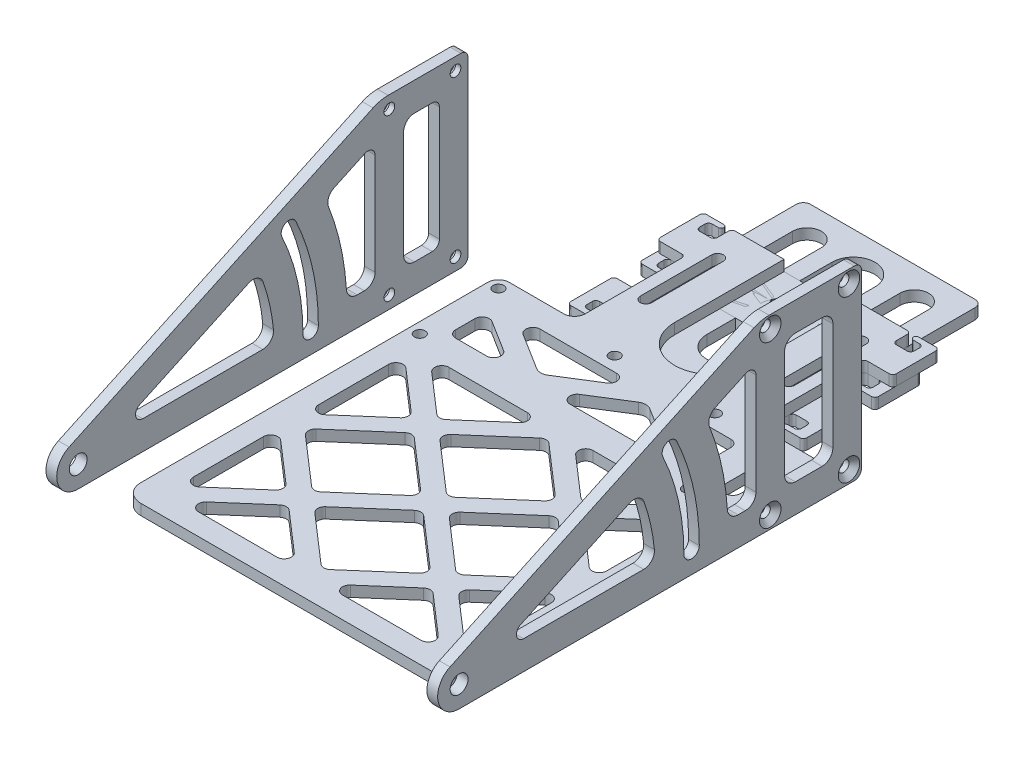
SolidWorks part; units mm, degrees
material "Thornel Mat VMA"
ref_plane "前视基准面" through (0, 0, 0) normal (0, 0, 1) x (1, 0, 0)
ref_plane "上视基准面" through (0, 0, 0) normal (0, 1, 0) x (1, 0, 0)
ref_plane "右视基准面" through (0, 0, 0) normal (1, 0, 0) x (0, 0, -1)
sketch "草图1" plane through (0, 0, 0) normal (1, 0, 0) x (0, 0, -1)
  line L0 (-53.59, 7.4702) -> (-112.5, -20) construction
  line L3 (0, 24) -> (0, -24)
  line L5 (-3.5, 22.5) -> (-3.5, -22.5) construction
  line L6 (-3.5, 22.5) -> (-25.5, 22.5) construction
  line L7 (-25.5, 22.5) -> (-25.5, -22.5) construction
  line L8 (-3.5, -22.5) -> (-25.5, -22.5) construction
  line L25 (-112.5, -26) -> (-2, -26)
  line L27 (-30.0591, 25.0631) -> (-115.0357, -14.5622)
  line L28 (-25.8329, 26) -> (-2, 26)
  line L29 (-112.5, -20) -> (-47.5, -20) construction
  circle A0 centre (-3.5, 22.5) radius 1.5
  circle A1 centre (-25.5, 22.5) radius 1.5
  circle A2 centre (-25.5, -22.5) radius 1.5
  circle A3 centre (-3.5, -22.5) radius 1.5
  arc A6 (-115.0357, -14.5622) -> (-112.5, -26) centre (-112.5, -20) ccw
  circle A7 centre (-112.5, -20) radius 2.5
  arc A8 (0, -24) -> (-2, -26) centre (-2, -24) cw
  arc A9 (-2, 26) -> (0, 24) centre (-2, 24) cw
  arc A11 (-47.5, -20) -> (-53.59, 7.4702) centre (-112.5, -20) ccw construction
  arc A12 (-45.35, -20) -> (-51.6414, 8.3788) centre (-112.5, -20) ccw
  arc A13 (-49.65, -20) -> (-55.5386, 6.5616) centre (-112.5, -20) ccw
  arc A14 (-49.65, -20) -> (-45.35, -20) centre (-47.5, -20) ccw
  arc A15 (-51.6414, 8.3788) -> (-55.5386, 6.5616) centre (-53.59, 7.4702) ccw
  arc A16 (-30.0591, 25.0631) -> (-25.8329, 26) centre (-25.8329, 16) cw
  point P20 (-49.0408, -5.9314)
  dimension "D5" = 3
  dimension "D6" = 3.5
  dimension "D10" = 4.3
  dimension "D11" = 3.5
  dimension "D12" = 65
  dimension "D3" = 6
  dimension "D4" = 5
  dimension "D8" = 2
  dimension "D9" = 112.5
  dimension "D14" = 10
  dimension "D1" = 22
  dimension "D2" = 45
  dimension "D7" = 3.5
  dimension "D13" = 25
extrude "凸台-拉伸1" add sketch "草图1" along normal blind 3 from offset 51.75
hole_wizard "孔1" positions "草图7" profile "草图8" legacy end condition through all
sketch "草图7" plane through (54.75, 0, 0) normal (1, 0, 0) x (0, 0, -1)
  point P0 (-25.5, 22.5)
  point P3 (-3.5, 22.5)
  point P6 (-3.5, -22.5)
  point P9 (-25.5, -22.5)
sketch "草图8" plane through (54.75, 22.5, 25.5) normal (0, 1, 0) x (0, 0, -1)
  line L0 (0, 0) -> (0, 3)
  line L1 (0, 3) -> (1.5, 3)
  line L2 (1.5, 3) -> (1.5, 1.5)
  line L3 (1.5, 1.5) -> (3, 0)
  line L4 (3, 0) -> (0, 0)
  line L5 (0, -6.4453) -> (0, 115.525) construction
  line L6 (-1.5, 1.5) -> (-3, 0) construction
  dimension "直径" = 3
  dimension "深度" = 3
  dimension "锥坑角度" = 90
  dimension "锥坑直径" = 6
sketch "草图11" plane through (54.75, 0, 0) normal (1, 0, 0) x (0, 0, -1)
  line L0 (-34.5101, -18) -> (-32.5, -18)
  line L1 (-25.5, 22.5) -> (-25.5, -22.5) construction
  line L2 (-29.5, 13.3574) -> (-29.5, -15)
  line L3 (-21.5, 15) -> (-21.5, -15)
  line L4 (-64.8817, -0.002) -> (-95.3024, -14.1874)
  line L5 (-29.5, 22.5) -> (-29.5, -22.5) construction
  line L6 (-21.5, 22.5) -> (-21.5, -22.5) construction
  line L7 (-18.5, -18) -> (-11, -18)
  line L8 (-103.4786, -18) -> (-8, -18)
  line L9 (-8, -18) -> (-8, 18)
  line L10 (-8, 18) -> (-25.8329, 18)
  line L11 (-26.6782, 17.8126) -> (-103.4786, -18)
  line L12 (-94.4572, -18) -> (-60.8916, -18)
  line L13 (-8, -15) -> (-8, 15)
  line L14 (-11, 18) -> (-18.5, 18)
  line L15 (-32.3452, 15.17) -> (-40.9719, 11.1473)
  arc A0 (-29.5, 13.3574) -> (-32.3452, 15.17) centre (-31.5, 13.3574) ccw
  arc A1 (-94.4572, -18) -> (-95.3024, -14.1874) centre (-94.4572, -16) cw
  arc A2 (-21.5, 15) -> (-18.5, 18) centre (-18.5, 15) cw
  arc A3 (-11, 18) -> (-8, 15) centre (-11, 15) cw
  arc A4 (-8, -15) -> (-11, -18) centre (-11, -15) cw
  arc A5 (-18.5, -18) -> (-21.5, -15) centre (-18.5, -15) cw
  arc A6 (-57.65, -20) -> (-62.789, 3.1806) centre (-112.5, -20) ccw
  arc A7 (-57.9056, -14.7107) -> (-60.7853, -1.7212) centre (-112.5, -20) ccw
  arc A8 (-25.8329, 18) -> (-26.6782, 17.8126) centre (-25.8329, 16) ccw
  arc A10 (-40.9719, 11.1473) -> (-42.4985, 7.3371) centre (-39.7041, 8.4284) ccw
  arc A11 (-37.35, -20) -> (-44.391, 11.7598) centre (-112.5, -20) ccw
  arc A12 (-37.504, -15.1919) -> (-42.4985, 7.3371) centre (-112.5, -20) ccw
  arc A13 (-29.5, -15) -> (-32.5, -18) centre (-32.5, -15) cw
  arc A14 (-34.5101, -18) -> (-37.504, -15.1919) centre (-34.5101, -15) cw
  arc A15 (-60.8916, -18) -> (-57.9056, -14.7107) centre (-60.8916, -15) ccw
  arc A16 (-64.8817, -0.002) -> (-60.7853, -1.7212) centre (-63.6139, -2.7209) cw
  dimension "D6" = 2
  dimension "D7" = 3
  dimension "D4" = 4
  dimension "D1" = 8
  dimension "D2" = 8
  dimension "D3" = 8
  dimension "D5" = 4
extrude "切除-拉伸2" cut sketch "草图11" against normal through all
mirror "镜向1" about plane through (0, 0, 0) normal (1, 0, 0) of bodies 121 106
sketch "草图2" plane through (-54.75, 0, 0) normal (-1, 0, 0) x (0, 0, 1)
  circle A0 centre (3.5, -22.5) radius 3 construction
  circle A3 centre (3.5, 22.5) radius 3 construction
  circle A4 centre (3.5, -22.5) radius 3
  circle A5 centre (3.5, 22.5) radius 3
extrude "凸台-拉伸2" add sketch "草图2" against normal up to surface (3 mm away) up to face at (-51.75, 0, 14.75)
sketch "草图4" plane through (-54.75, 0, 0) normal (-1, 0, 0) x (0, 0, 1)
  line L1 (25.5, 22.5) -> (7, 22.5) construction
  line L2 (25.5, 22.5) -> (25.5, -22.5) construction
  line L3 (25.5, -22.5) -> (7, -22.5) construction
  line L4 (7, 22.5) -> (7, -22.5) construction
  line L5 (0, 26) -> (3.5, 26)
  line L6 (0, 26) -> (0, -26)
  line L7 (0, -26) -> (3.5, -26)
  line L12 (3.5, 26) -> (3.5, -26)
  line L13 (2, 26) -> (25.8329, 26) construction
  line L14 (112.5, -26) -> (2, -26) construction
  line L15 (0, -24) -> (0, 24) construction
  circle A1 centre (25.5, 22.5) radius 1.5 construction
  circle A8 centre (7, -22.5) radius 1.5
  circle A9 centre (7, 22.5) radius 1.5
  dimension "D1" = 18.5
  dimension "D2" = 3.5
extrude "切除-拉伸1" cut sketch "草图4" against normal through all
other "移动面1" face at (-53.25, -16.8107, 9.1893) face at (-53.25, 16.8107, 9.1893) face at (-53.25, 0, 8) offset 3.5 parameters "D1"=3.5
fillet "圆角3" radius 2 4 edges at (-53.25, -26, 3.5) (-53.25, 26, 3.5) (-53.25, -18, 11.5) (-53.25, 18, 11.5)
hole_wizard "孔2" positions "草图9" profile "草图10" legacy end condition through all
sketch "草图9" plane through (-54.75, 0, 0) normal (-1, 0, 0) x (0, 0, 1)
  point P0 (7, 22.5)
  point P3 (7, -22.5)
sketch "草图10" plane through (-54.75, 22.5, 7) normal (0, 1, 0) x (0, 0, 1)
  line L0 (0, 0) -> (0, 109.5)
  line L1 (0, 109.5) -> (1.5, 109.5)
  line L2 (1.5, 109.5) -> (1.5, 1.5)
  line L3 (1.5, 1.5) -> (3, 0)
  line L4 (3, 0) -> (0, 0)
  line L5 (0, -6.4453) -> (0, 115.525) construction
  line L6 (-1.5, 1.5) -> (-3, 0) construction
  dimension "直径" = 3
  dimension "深度" = 109.5
  dimension "锥坑角度" = 90
  dimension "锥坑直径" = 6
ref_plane "基准面1" through (0, -27.7, 0) normal (0, -1, 0) x (-1, 0, 0)
sketch "草图5" plane through (0, -27.7, 0) normal (0, -1, 0) x (-1, 0, 0)
  line L0 (0, 0) -> (0, 43.5) construction
  line L3 (-33, 43.5) -> (-27.25, 43.5)
  line L4 (46.25, -100.5) -> (46.25, -3.5)
  line L5 (-20, 34.5) -> (-20, 14.5) construction
  line L6 (-31.75, -3.5) -> (43.25, -3.5) construction
  line L7 (-31.75, -3.5) -> (-31.75, -25.5) construction
  line L8 (-31.75, -25.5) -> (43.25, -25.5) construction
  line L9 (43.25, -3.5) -> (43.25, -25.5) construction
  line L11 (28, -0.5) -> (43.25, -0.5)
  line L12 (-18.4, 34.5) -> (-18.4, 14.5)
  line L13 (-21.6, 34.5) -> (-21.6, 14.5)
  line L14 (-25, 43.5) -> (25, 43.5)
  line L16 (-30, 42) -> (-30, 38.5)
  line L17 (-30, 38.5) -> (-25, 38.5)
  line L18 (-25, 43.5) -> (-25, 38.5)
  line L19 (-33, 30.5) -> (-33, 43.5)
  line L20 (-33, 30.5) -> (-25, 30.5)
  line L22 (-43.25, -0.5) -> (-28, -0.5)
  line L23 (-25, 30.5) -> (-25, 2.5)
  line L24 (-20, 34.5) -> (-25, 34.5) construction
  line L25 (-25, 30.5) -> (-25, 38.5) construction
  line L26 (0, 28.6) -> (0, -28.6) construction
  line L27 (25, 30.5) -> (25, 38.5) construction
  line L28 (20, 34.5) -> (25, 34.5) construction
  line L29 (25, 30.5) -> (25, 2.5)
  line L30 (33, 30.5) -> (25, 30.5)
  line L31 (33, 30.5) -> (33, 43.5)
  line L32 (25, 43.5) -> (25, 38.5)
  line L33 (30, 38.5) -> (25, 38.5)
  line L34 (30, 42) -> (30, 38.5)
  line L35 (33, 43.5) -> (27.25, 43.5)
  line L36 (20, 34.5) -> (20, 14.5) construction
  line L37 (18.4, 34.5) -> (18.4, 14.5)
  line L38 (21.6, 34.5) -> (21.6, 14.5)
  line L43 (41.25, -105.5) -> (-41.25, -105.5)
  line L44 (-46.25, -100.5) -> (-46.25, -3.5)
  line L45 (-30, 42) -> (-27.25, 42)
  line L46 (30, 42) -> (27.25, 42)
  arc A0 (-18.4, 34.5) -> (-21.6, 34.5) centre (-20, 34.5) ccw
  circle A1 centre (-31.75, -25.5) radius 1.5
  arc A2 (-21.6, 14.5) -> (-18.4, 14.5) centre (-20, 14.5) ccw
  arc A4 (-28, -0.5) -> (-25, 2.5) centre (-28, 2.5) ccw
  arc A5 (28, -0.5) -> (25, 2.5) centre (28, 2.5) cw
  arc A6 (18.4, 34.5) -> (21.6, 34.5) centre (20, 34.5) cw
  circle A7 centre (10.75, -3.5) radius 1.5
  circle A8 centre (-17.25, -3.5) radius 1.5
  circle A9 centre (-31.75, -3.5) radius 1.5
  circle A10 centre (43.25, -3.5) radius 1.5
  circle A11 centre (43.25, -25.5) radius 1.5
  arc A12 (43.25, -0.5) -> (46.25, -3.5) centre (43.25, -3.5) cw
  arc A16 (21.6, 14.5) -> (18.4, 14.5) centre (20, 14.5) cw
  arc A21 (46.25, -100.5) -> (41.25, -105.5) centre (41.25, -100.5) cw
  arc A22 (-43.25, -0.5) -> (-46.25, -3.5) centre (-43.25, -3.5) ccw
  arc A23 (-46.25, -100.5) -> (-41.25, -105.5) centre (-41.25, -100.5) ccw
  arc A24 (-27.25, 43.5) -> (-27.25, 42) centre (-27.25, 42.75) cw
  arc A25 (27.25, 43.5) -> (27.25, 42) centre (27.25, 42.75) ccw
  point P3 (-20, 24.5)
  point P62 (20, 24.5)
  point P70 (-26.5, 42.75)
  dimension "D5" = 3
  dimension "D8" = 28
  dimension "D9" = 14.5
  dimension "D12" = 3
  dimension "D13" = 8
  dimension "D17" = 50
  dimension "D18" = 5
  dimension "D6" = 3
  dimension "D20" = 1.5
  dimension "D1" = 3.5
  dimension "D2" = 22
  dimension "D3" = 75
  dimension "D4" = 31.75
  dimension "D7" = 43.5
  dimension "D10" = 20
  dimension "D11" = 3.2
  dimension "D14" = 5
  dimension "D15" = 5
  dimension "D16" = 5
  dimension "D19" = 80
  dimension "D21" = 1.5
extrude "凸台-拉伸3" add sketch "草图5" along normal blind 3 separate body
sketch "草图6" plane through (0, -30.7, 0) normal (0, -1, 0) x (1, 0, 0)
  line L0 (33, -30.5) -> (25, -30.5) construction
  line L1 (33, -43.5) -> (33, -30.5) construction
  line L2 (30, -38.5) -> (30, -42) construction
  line L3 (25, -38.5) -> (30, -38.5) construction
  line L4 (30, -30.5) -> (25, -30.5)
  line L5 (33, -38.5) -> (33, -25.5)
  line L6 (30, -27) -> (30, -30.5)
  line L7 (25, -38.5) -> (33, -38.5)
  line L9 (25, -30.5) -> (25, -2.5) construction
  line L10 (25, -30.5) -> (25, -25.5)
  line L11 (25, -43.5) -> (25, -38.5) construction
  line L12 (25, -61.5) -> (25, -38.5)
  line L13 (25, -25.5) -> (-25, -25.5)
  line L14 (23, -63.5) -> (-23, -63.5)
  line L15 (-25, -43.5) -> (25, -43.5) construction
  line L16 (0, -28.6) -> (0, 28.6) construction
  line L17 (-25, -61.5) -> (-25, -38.5)
  line L18 (-25, -30.5) -> (-25, -25.5)
  line L20 (-25, -38.5) -> (-33, -38.5)
  line L21 (-30, -27) -> (-30, -30.5)
  line L22 (-33, -38.5) -> (-33, -25.5)
  line L23 (-30, -30.5) -> (-25, -30.5)
  line L24 (33, -25.5) -> (27.25, -25.5)
  line L25 (27.25, -27) -> (30, -27)
  line L26 (27.25, -42.75) -> (27.25, -26.25) construction
  line L27 (-27.25, -27) -> (-30, -27)
  line L28 (-33, -25.5) -> (-27.25, -25.5)
  circle A0 centre (20, -34.5) radius 1.5
  circle A1 centre (-20, -34.5) radius 1.5
  arc A2 (25, -61.5) -> (23, -63.5) centre (23, -61.5) cw
  arc A3 (-25, -61.5) -> (-23, -63.5) centre (-23, -61.5) ccw
  arc A4 (27.25, -27) -> (27.25, -25.5) centre (27.25, -26.25) cw
  arc A5 (-27.25, -27) -> (-27.25, -25.5) centre (-27.25, -26.25) ccw
  dimension "D1" = 3
  dimension "D3" = 2
  dimension "D2" = 20
extrude "凸台-拉伸4" add sketch "草图6" along normal blind 3 separate body
fillet "圆角1" radius 1 14 edges at (25, -29.2, -30.5) (33, -29.2, -30.5) (33, -29.2, -43.5) (30, -29.2, -38.5) (25, -29.2, -38.5) (25, -29.2, -43.5) (-25, -29.2, -43.5) (-25, -29.2, -38.5) (-25, -29.2, -30.5) (-33, -29.2, -30.5) (-33, -29.2, -43.5) (-30, -29.2, -38.5) (30, -29.2, -42) (-30, -29.2, -42)
fillet "圆角2" radius 1 14 edges at (25, -32.2, -30.5) (30, -32.2, -30.5) (33, -32.2, -38.5) (25, -32.2, -38.5) (-25, -32.2, -38.5) (-33, -32.2, -38.5) (-30, -32.2, -30.5) (-25, -32.2, -30.5) (-25, -32.2, -25.5) (25, -32.2, -25.5) (33, -32.2, -25.5) (30, -32.2, -27) (-33, -32.2, -25.5) (-30, -32.2, -27)
sketch "草图12" plane through (0, -33.7, 0) normal (0, -1, 0) x (1, 0, 0)
  line L0 (-15, -42.5) -> (-15, -54.5) construction
  line L1 (-11, -42.5) -> (-11, -54.5)
  line L2 (-19, -42.5) -> (-19, -54.5)
  line L3 (0, -37.5) -> (0, -52.5) construction
  line L4 (6, -37.5) -> (6, -52.5)
  line L5 (-6, -37.5) -> (-6, -52.5)
  line L8 (-23, -58.5) -> (23, -58.5)
  line L9 (-23, -58.5) -> (23, -58.5) construction
  line L10 (-25, -39.5) -> (-25, -61.5) construction
  line L11 (24, -25.5) -> (-24, -25.5) construction
  line L12 (0, -32.835) -> (0, 32.835) construction
  line L16 (15, -42.5) -> (15, -54.5) construction
  line L17 (11, -42.5) -> (11, -54.5)
  line L18 (19, -42.5) -> (19, -54.5)
  arc A0 (-11, -42.5) -> (-19, -42.5) centre (-15, -42.5) ccw
  arc A1 (-19, -54.5) -> (-11, -54.5) centre (-15, -54.5) ccw
  arc A2 (6, -37.5) -> (-6, -37.5) centre (0, -37.5) ccw
  arc A3 (-6, -52.5) -> (6, -52.5) centre (0, -52.5) ccw
  arc A6 (11, -42.5) -> (19, -42.5) centre (15, -42.5) cw
  arc A7 (19, -54.5) -> (11, -54.5) centre (15, -54.5) cw
  point P2 (-15, -48.5)
  point P7 (0, -45)
  point P24 (0, -31.5)
  point P38 (15, -48.5)
  dimension "D1" = 5
  dimension "D2" = 6
  dimension "D3" = 12
  dimension "D4" = 5
  dimension "D5" = 12
  dimension "D6" = 6
extrude "切除-拉伸3" cut sketch "草图12" against normal through all
sketch "草图13" plane through (0, -30.7, 0) normal (0, -1, 0) x (1, 0, 0)
  line L0 (38, 19.25) -> (38, 9.75) construction
  line L1 (-40.25, 99.5) -> (40.25, 99.5)
  line L2 (-40.25, 99.5) -> (-40.25, 29.5)
  line L3 (-40.25, 29.5) -> (40.25, 29.5)
  line L4 (40.25, 99.5) -> (40.25, 29.5)
  line L5 (-39.25, 21.5) -> (27.75, 21.5)
  line L6 (-39.25, 21.5) -> (-39.25, 7.5)
  line L7 (-39.25, 7.5) -> (27.75, 7.5)
  line L8 (27.75, 21.5) -> (27.75, 7.5)
  line L13 (40.25, 19.25) -> (40.25, 9.75)
  line L14 (35.75, 19.25) -> (35.75, 9.75)
  line L16 (-46.25, 100.5) -> (-46.25, 3.5) construction
  line L17 (41.25, 105.5) -> (-41.25, 105.5) construction
  line L18 (46.25, 3.5) -> (46.25, 100.5) construction
  line L24 (0, -43.5) -> (0, -12.9) construction
  line L25 (-24, -43.5) -> (24, -43.5) construction
  line L26 (-10.4, -43.5) -> (-10.4, -12.9)
  line L27 (10.4, -43.5) -> (10.4, -12.9)
  line L28 (-18.4, -34.5) -> (-18.4, -14.5) construction
  arc A0 (40.25, 19.25) -> (35.75, 19.25) centre (38, 19.25) ccw
  arc A1 (35.75, 9.75) -> (40.25, 9.75) centre (38, 9.75) ccw
  circle A2 centre (-43.25, 25.5) radius 1.5 construction
  circle A3 centre (-43.25, 3.5) radius 1.5 construction
  circle A4 centre (31.75, 25.5) radius 1.5 construction
  circle A5 centre (31.75, 3.5) radius 1.5 construction
  arc A6 (-10.4, -43.5) -> (10.4, -43.5) centre (0, -43.5) ccw
  arc A7 (10.4, -12.9) -> (-10.4, -12.9) centre (0, -12.9) ccw
  circle A8 centre (-10.75, 3.5) radius 1.5 construction
  point P10 (38, 14.5)
  point P33 (0, -28.2)
  point P41 (-18.4, -24.5)
  point P46 (0, -2.5)
  dimension "D1" = 4
  dimension "D2" = 4
  dimension "D7" = 4
  dimension "D9" = 4
  dimension "D11" = 6
  dimension "D3" = 6
  dimension "D4" = 6
  dimension "D5" = 6
  dimension "D6" = 4
  dimension "D8" = 4
  dimension "D10" = 8
extrude "切除-拉伸4" cut sketch "草图13" against normal through all
sketch "草图14" plane through (0, -30.7, 0) normal (0, -1, 0) x (1, 0, 0)
  line L0 (-39.25, 7.5) -> (-16.9167, 21.5)
  line L1 (27.75, 21.5) -> (-39.25, 21.5) construction
  line L2 (-16.9167, 21.5) -> (5.4167, 7.5)
  line L3 (-39.25, 7.5) -> (27.75, 7.5) construction
  line L4 (5.4167, 7.5) -> (27.75, 21.5)
  line L5 (-40.25, 99.5) -> (40.25, 29.5)
  line L6 (-40.25, 29.5) -> (40.25, 99.5)
  line L7 (0, 99.5) -> (-40.25, 64.5)
  line L8 (40.25, 99.5) -> (-40.25, 99.5) construction
  line L9 (-40.25, 99.5) -> (-40.25, 29.5) construction
  line L10 (-40.25, 64.5) -> (0, 29.5)
  line L11 (-40.25, 29.5) -> (40.25, 29.5) construction
  line L12 (0, 29.5) -> (40.25, 64.5)
  line L13 (40.25, 29.5) -> (40.25, 99.5) construction
  line L14 (40.25, 64.5) -> (0, 99.5)
extrude "拉伸-薄壁1" add sketch "草图14" against normal up to surface (3 mm away) thin up to face at (0, -27.7, 64.5) thin type mid plane wall 5
fillet "圆角4" radius 3 2 edges at (5.4167, -29.2, 10.4506) (-16.9167, -29.2, 18.5494)
fillet "圆角5" radius 2 50 edges at (-12.2098, -29.2, 21.5) (23.0431, -29.2, 21.5) (-21.6236, -29.2, 21.5) (-34.5431, -29.2, 7.5) (0.7098, -29.2, 7.5) (27.75, -29.2, 7.5) (10.1236, -29.2, 7.5) (27.75, -29.2, 18.5494) (20.125, -29.2, 78.687) (36.4401, -29.2, 64.5) (20.125, -29.2, 50.313) (3.8099, -29.2, 64.5) (0, -29.2, 96.187) (16.3151, -29.2, 82) (0, -29.2, 67.813) (-16.3151, -29.2, 82) (16.3151, -29.2, 47) (0, -29.2, 32.813) (-16.3151, -29.2, 47) (0, -29.2, 61.187) (-3.8099, -29.2, 64.5) (-20.125, -29.2, 50.313) (-36.4401, -29.2, 64.5) (-20.125, -29.2, 78.687) (-40.25, -29.2, 61.187) (-23.9349, -29.2, 47) (-40.25, -29.2, 32.813) (-3.8099, -29.2, 99.5) (-20.125, -29.2, 85.313) (-36.4401, -29.2, 99.5) (-20.125, -29.2, 43.687) (-3.8099, -29.2, 29.5) (-36.4401, -29.2, 29.5) (20.125, -29.2, 85.313) (3.8099, -29.2, 99.5) (36.4401, -29.2, 99.5) (40.25, -29.2, 67.813) (23.9349, -29.2, 82) (40.25, -29.2, 96.187) (23.9349, -29.2, 47) (40.25, -29.2, 61.187) (40.25, -29.2, 32.813) (-23.9349, -29.2, 82) (-40.25, -29.2, 67.813) (-40.25, -29.2, 96.187) (3.8099, -29.2, 29.5) (20.125, -29.2, 43.687) (36.4401, -29.2, 29.5) (-39.25, -29.2, 10.4506) (-39.25, -29.2, 21.5)
pattern_linear "阵列(线性)1" count 2 spacing 20 along (0, 0, 1) of bodies 123 114
